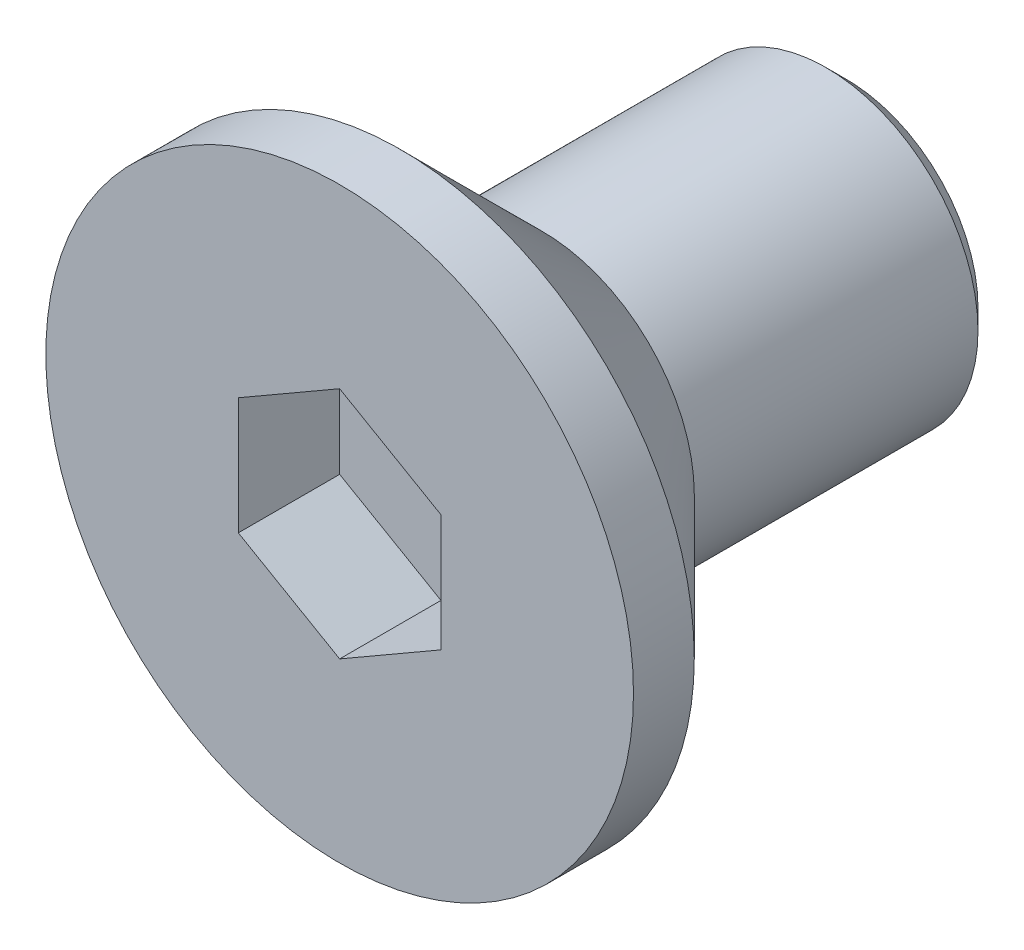
SolidWorks part; units mm, degrees
material "1.4000 (X6Cr13)"
ref_plane "Ebene vorne" through (0, 0, 0) normal (0, 0, 1) x (1, 0, 0)
ref_plane "Ebene oben" through (0, 0, 0) normal (0, 1, 0) x (1, 0, 0)
ref_plane "Ebene rechts" through (0, 0, 0) normal (1, 0, 0) x (0, 0, -1)
sketch "Skizze1" plane through (0, 0, 0) normal (1, 0, 0) x (0, 0, -1)
  line L0 (-31.7636, 0) -> (42.9935, 0) construction
  line L1 (0, 26.0256) -> (0, -29.3045) construction
  line L2 (0, 0) -> (0, 2.9)
  line L3 (0.6, 2.9) -> (2, 1.5)
  line L4 (2, 1.5) -> (5, 1.5)
  line L5 (5, 1.5) -> (5, 0)
  line L6 (5, 0) -> (0, 0)
  line L7 (0, 2.9) -> (0.6, 2.9)
  dimension "D1" = 3
  dimension "D2" = 5
  dimension "D3" = 5.8
  dimension "D4" = 45
  dimension "D5" = 2
  dimension "D6" = 0.6
revolve "Rotation1" add sketch "Skizze1" angle 360 about L0
sketch "Skizze3" plane through (0, 0, 0) normal (0, 0, 1) x (1, 0, 0)
  line L0 (0, 1.5356) -> (0, -1.3958) construction
  line L1 (-1.5297, 0) -> (1.3792, 0) construction
  line L3 (1, -0.5774) -> (1, 0.5774)
  line L4 (1, 0.5774) -> (0, 1.1547)
  line L5 (0, 1.1547) -> (-1, 0.5774)
  line L6 (-1, 0.5774) -> (-1, -0.5774)
  line L7 (-1, -0.5774) -> (0, -1.1547)
  line L8 (0, -1.1547) -> (1, -0.5774)
  circle A0 centre (0, 0) radius 1 construction
  dimension "D1" = 2
extrude "Schnitt-Linear austragen1" cut sketch "Skizze3" against normal blind 1
chamfer "Fase1" distance 0.2 angle 45 1 edges at (1.5, 0, -5)
ref_axis "Achse1" through (0, 0, 0.3) along (0, 0, -1)
